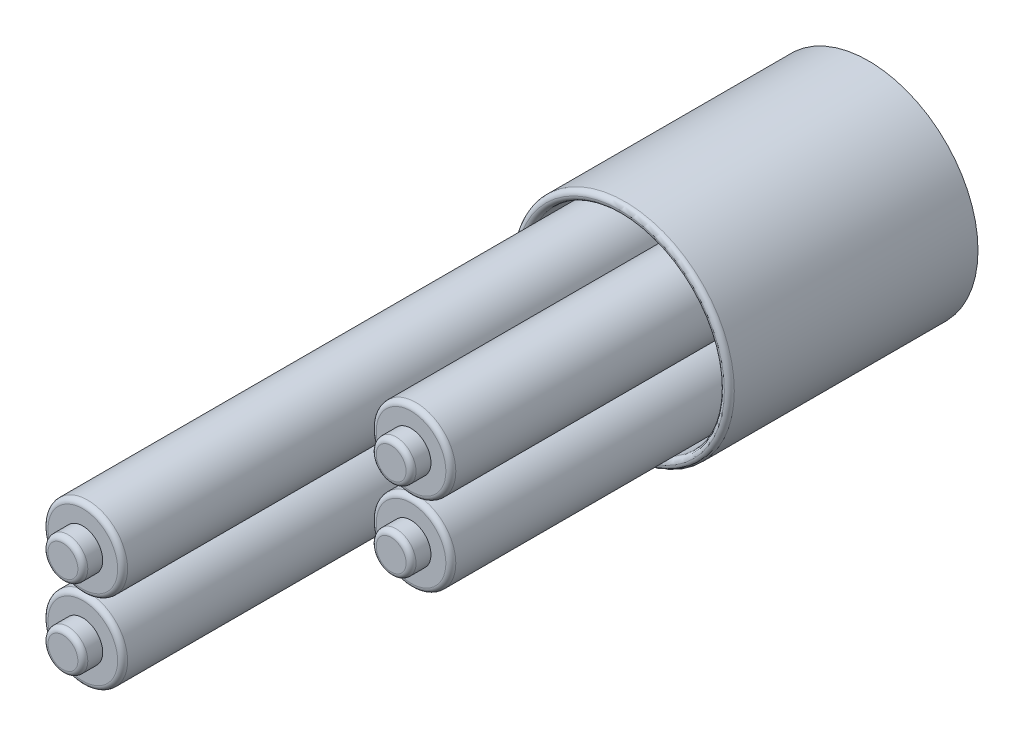
SolidWorks part; units mm, degrees
material "PBT General Purpose"
ref_plane "Front Plane" through (0, 0, 0) normal (0, 0, 1) x (1, 0, 0)
ref_plane "Top Plane" through (0, 0, 0) normal (0, 1, 0) x (1, 0, 0)
ref_plane "Right Plane" through (0, 0, 0) normal (1, 0, 0) x (0, 0, -1)
sketch "Sketch1" plane through (0, 0, 0) normal (0, 0, 1) x (1, 0, 0)
  line L5 (0, 0.1016) -> (0, -0.1016) construction
  line L6 (-0.1016, 0) -> (0.1016, 0) construction
  circle A0 centre (-0.1016, 0.1016) radius 0.1016
  circle A1 centre (0.1016, 0.1016) radius 0.1016
  circle A2 centre (-0.1016, -0.1016) radius 0.1016
  circle A3 centre (0.1016, -0.1016) radius 0.1016
  circle A4 centre (0, 0) radius 0.254
  circle A5 centre (-0.1016, -0.1016) radius 0.1016
  circle A6 centre (0.1016, -0.1016) radius 0.1016
  circle A7 centre (-0.1016, 0.1016) radius 0.0508
  circle A8 centre (0.1016, 0.1016) radius 0.0508
  circle A9 centre (0.1016, -0.1016) radius 0.0508
  circle A10 centre (-0.1016, -0.1016) radius 0.0508
  circle A11 centre (0, 0) radius 0.2794
  point P0 (0, 0)
extrude "Boss-Extrude4" add sketch "Sketch1" along normal blind 1.905 separate body contours A2 region at (-0.0318, -0.0318, 0)
extrude "Boss-Extrude9" add sketch "Sketch1<12>" along normal blind 1.27 contours A1 A8 region at (0.1016, 0.2003, 0)
sketch "Sketch1<12>" plane through (0, 0, 0) normal (0, 0, 1) x (1, 0, 0) same geometry as "Sketch1"
extrude "Boss-Extrude10" add sketch "Sketch1<13>" along normal blind 1.27 contours A3 A9 region at (0.1714, -0.0318, 0)
sketch "Sketch1<13>" plane through (0, 0, 0) normal (0, 0, 1) x (1, 0, 0) same geometry as "Sketch1"
extrude "Boss-Extrude11" add sketch "Sketch1<14>" along normal blind 0.635 separate body contours A11 A4 region at (-0.2715, 0, 0)
sketch "Sketch1<14>" plane through (0, 0, 0) normal (0, 0, 1) x (1, 0, 0) same geometry as "Sketch1"
extrude "Boss-Extrude12" add sketch "Sketch1<15>" along normal blind 1.905 separate body contours A0 A7 region at (-0.0318, 0.0318, 0)
sketch "Sketch1<15>" plane through (0, 0, 0) normal (0, 0, 1) x (1, 0, 0) same geometry as "Sketch1"
extrude "Boss-Extrude14" add sketch "Sketch1<17>" along normal blind 1.3208 separate body contours A8 region at (0.1016, 0.1016, 0)
sketch "Sketch1<17>" plane through (0, 0, 0) normal (0, 0, 1) x (1, 0, 0) same geometry as "Sketch1"
fillet "Fillet2" radius 0.0127 1 edges at (0.1524, 0.1016, 1.3208)
fillet "Fillet5" radius 0.0127 2 edges at (0.2794, 0, 0.635) (0.254, 0, 0.635)
extrude "Boss-Extrude15" add sketch "Sketch1<18>" along normal blind 1.3208 separate body contours A9 region at (0.1016, -0.1016, 0)
sketch "Sketch1<18>" plane through (0, 0, 0) normal (0, 0, 1) x (1, 0, 0) same geometry as "Sketch1"
fillet "Fillet6" radius 0.0127 1 edges at (0.1524, -0.1016, 1.3208)
extrude "Boss-Extrude17" add sketch "Sketch1<20>" along normal blind 1.9558 separate body contours A10 region at (-0.1016, -0.1016, 0)
sketch "Sketch1<20>" plane through (0, 0, 0) normal (0, 0, 1) x (1, 0, 0) same geometry as "Sketch1"
fillet "Fillet7" radius 0.0127 1 edges at (-0.0508, -0.1016, 1.9558)
extrude "Boss-Extrude19" add sketch "Sketch1<22>" along normal blind 1.9558 separate body contours A7
sketch "Sketch1<22>" plane through (0, 0, 0) normal (0, 0, 1) x (1, 0, 0) same geometry as "Sketch1"
fillet "Fillet8" radius 0.0127 1 edges at (-0.0508, 0.1016, 1.9558)
fillet "Fillet9" radius 0.0127 1 edges at (0, -0.1016, 1.905)
fillet "Fillet10" radius 0.0127 1 edges at (0.2032, -0.1016, 1.27)
fillet "Fillet11" radius 0.0127 1 edges at (0.2032, 0.1016, 1.27)
fillet "Fillet12" radius 0.0127 1 edges at (0, 0.1016, 1.905)
